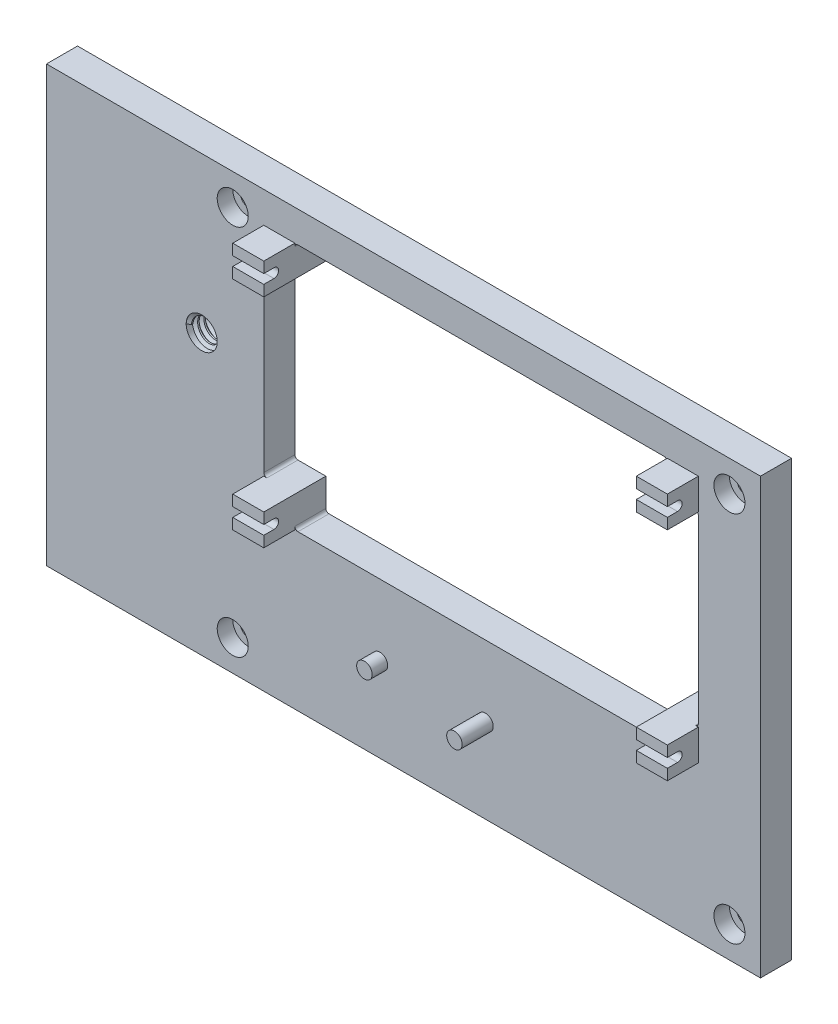
SolidWorks part; units mm, degrees
material "1.0558 (G300)"
ref_plane "Front Plane" through (0, 0, 0) normal (0, 0, 1) x (1, 0, 0)
ref_plane "Top Plane" through (0, 0, 0) normal (0, 1, 0) x (1, 0, 0)
ref_plane "Right Plane" through (0, 0, 0) normal (1, 0, 0) x (0, 0, -1)
sketch "Croquis1" plane through (0, 0, 0) normal (0, 0, 1) x (1, 0, 0)
  line L0 (-90, 0) -> (-70, 0) construction
  line L1 (90, -50) -> (-90, -50)
  line L2 (90, -50) -> (90, 50)
  line L3 (90, 50) -> (-90, 50)
  line L4 (-90, -50) -> (-90, 50)
  line L5 (-60, 30) -> (-70, 30)
  line L6 (60, 30) -> (60, 40)
  line L7 (90, 0) -> (70, 0) construction
  line L8 (0, 50) -> (0, 40) construction
  line L9 (0, -50) -> (0, -40) construction
  line L10 (-70, 0) -> (-70, 30)
  line L11 (-60, 40) -> (60, 40)
  line L12 (70, 30) -> (70, -30)
  line L13 (60, -40) -> (-60, -40)
  line L14 (-70, -30) -> (-70, 0)
  line L15 (-70, 0) -> (-60, 0) construction
  line L16 (0, 40) -> (0, 30) construction
  line L17 (-60, 40) -> (-60, 30)
  line L18 (60, 30) -> (70, 30)
  line L19 (-60, -30) -> (-70, -30)
  line L20 (-60, -30) -> (-60, -40)
  line L21 (60, -30) -> (60, -40)
  line L22 (60, -30) -> (70, -30)
  point P0 (0, 0)
  dimension "D1" = 180
  dimension "D2" = 100
  dimension "D3" = 20
  dimension "D4" = 20
  dimension "D5" = 10
  dimension "D6" = 10
  dimension "D7" = 10
  dimension "D8" = 10
  dimension "D9" = 10
  dimension "D10" = 10
  dimension "D11" = 120
  dimension "D12" = 10
  dimension "D13" = 10
  dimension "D14" = 10
extrude "Saliente-Extruir1" add sketch "Croquis1" along normal blind 10
sketch "Croquis2" plane through (0, 0, 10) normal (0, 0, 1) x (1, 0, 0)
  line L0 (80, 50) -> (80, 40) construction
  line L1 (90, 50) -> (-90, 50) construction
  line L2 (80, 40) -> (90, 40) construction
  line L3 (90, -50) -> (90, 50) construction
  line L4 (0, 24.0798) -> (0, -11.3446) construction
  line L5 (-15.0818, 0) -> (14.1818, 0) construction
  line L6 (-80, 40) -> (-90, 40) construction
  line L7 (-80, 50) -> (-80, 40) construction
  line L8 (80, -40) -> (90, -40) construction
  line L9 (80, -40) -> (80, -80)
  line L10 (-80, -40) -> (-90, -40) construction
  line L11 (-80, -40) -> (-80, -80)
  dimension "D1" = 10
  dimension "D2" = 10
sketch "Croquis4" plane through (0, 0, 10) normal (0, 0, 1) x (1, 0, 0)
  line L0 (0, 57.0372) -> (0, -6.8385) construction
  line L1 (-60, -30) -> (-70, -30)
  line L2 (-60, -30) -> (-60, -40)
  line L3 (-60, -40) -> (-70, -40)
  line L4 (-70, -30) -> (-70, -40)
  line L5 (-11.0869, 0) -> (22.8375, 0) construction
  line L6 (70, -30) -> (70, -40)
  line L7 (60, -40) -> (70, -40)
  line L8 (60, -30) -> (60, -40)
  line L9 (60, -30) -> (70, -30)
  line L10 (60, 30) -> (70, 30)
  line L11 (60, 30) -> (60, 40)
  line L12 (60, 40) -> (70, 40)
  line L13 (70, 30) -> (70, 40)
  line L14 (-60, 40) -> (-70, 40)
  line L15 (-70, 30) -> (-70, 40)
  line L16 (-60, 30) -> (-70, 30)
  line L17 (-60, 30) -> (-60, 40)
  dimension "D1" = 10
  dimension "D2" = 10
extrude "Saliente-Extruir2" add sketch "Croquis4" along normal blind 10
sketch "Croquis5" plane through (60, 0, 0) normal (-1, 0, 0) x (0, 0, 1)
  line L4 (10, 50) -> (10, -50) construction
  line L6 (10, 36.5) -> (11.5, 36.5) construction
  line L7 (10, 33.5) -> (11.5, 33.5) construction
  line L11 (20, 36.5) -> (20, 33.5)
  line L12 (20, 30) -> (20, 40) construction
  line L14 (20, 33.5) -> (16.7205, 33.5)
  line L15 (16.7205, 36.5) -> (20, 36.5)
  arc A1 (16.7205, 36.5) -> (16.7205, 33.5) centre (16.7205, 35) ccw
extrude "Cortar-Extruir1" cut sketch "Croquis5" against normal through all
mirror "Simetría1" about plane through (0, 0, 0) normal (0, 1, 0) of "Cortar-Extruir1"
mirror "Simetría2" about plane through (0, 0, 0) normal (1, 0, 0) of "Simetría1"
fillet "Redondeo1" radius 1 1 edges at (-70, -30, 5)
fillet "Redondeo2" radius 1 7 edges at (60, -40, 5) (70, -30, 5) (70, 30, 5) (60, 40, 5) (-60, 40, 5) (-70, 30, 5) (-60, -40, 5)
sketch "Croquis7" plane through (0, -50, 0) normal (0, -1, 0) x (1, 0, 0)
  line L1 (-90, 10) -> (90, 10)
  line L2 (-90, 10) -> (-90, 0)
  line L3 (-90, 0) -> (90, 0)
  line L4 (90, 10) -> (90, 0)
extrude "Saliente-Extruir4" add sketch "Croquis7" along normal blind 40
hole_wizard "Taladro1" positions "Croquis3D1" profile "Croquis3" legacy
sketch3d "Croquis3D1"
  point P0 (-80, 40, 10)
  point P3 (80, 40, 10)
  point P36 (-80, -80, 10)
  point P40 (80, -80, 10)
sketch "Croquis3" plane through (-80, 40, 10) normal (1, 0, 0) x (0, -1, 0)
  line L0 (0, 0) -> (0, 10)
  line L1 (0, 10) -> (2.5, 10)
  line L2 (2.5, 10) -> (2.5, 5)
  line L3 (2.5, 5) -> (5, 5)
  line L4 (5, 5) -> (5, 0)
  line L5 (5, 0) -> (0, 0)
  line L6 (0, 110) -> (0, -10) construction
  dimension "Diámetro" = 5
  dimension "Profundidad" = 10
  dimension "Diámetro de refrentado 1" = 10
  dimension "Profundidad de refrentado 1" = 5
sketch "Croquis8" plane through (0, 0, 10) normal (0, 0, 1) x (1, 0, 0)
  line L0 (-70, -40) -> (-70, -62.9) construction
  line L1 (-70, -62.9) -> (-32.5848, -62.9) construction
  circle A0 centre (-32.5848, -62.9) radius 2.5
  dimension "D1" = 5
  dimension "D2" = 22.9
  dimension "D3" = 37.4152
extrude "Saliente-Extruir5" add sketch "Croquis8" along normal blind 5
sketch "Croquis9" plane through (0, 0, 10) normal (0, 0, 1) x (1, 0, 0)
  line L0 (-30.0848, -62.9) -> (1.4152, -62.9) construction
  circle A0 centre (-32.5848, -62.9) radius 2.5 construction
  circle A1 centre (-32.5848, -62.9) radius 2.5 construction
  circle A2 centre (1.4152, -62.9) radius 2.5
  dimension "D2" = 5
  dimension "D1" = 31.5
extrude "Saliente-Extruir6" add sketch "Croquis9" along normal blind 10
sketch "Croquis10" plane through (-90, 0, 0) normal (-1, 0, 0) x (0, 0, 1)
  line L1 (0, 50) -> (10, 50)
  line L2 (0, 50) -> (0, -90)
  line L3 (0, -90) -> (10, -90)
  line L4 (10, 50) -> (10, -90)
extrude "Saliente-Extruir7" add sketch "Croquis10" along normal blind 50
sketch "Croquis11" plane through (0, 0, 10) normal (0, 0, 1) x (1, 0, 0)
  point P6 (-90, 0)
hole_wizard "Taladros de espiga de Ø10.0mm1" positions "Croquis3D2" profile "Croquis12" hole size "Ø10.0" standard "Ansi Metric"
sketch3d "Croquis3D2"
  point P0 (-90, 0, 10)
sketch "Croquis12" plane through (-90, 0, 10) normal (1, 0, 0) x (0, -1, 0)
  line L0 (0, 0) -> (0, 13.0043)
  line L1 (0, 13.0043) -> (5, 10)
  line L2 (5, 10) -> (5, 0)
  line L5 (5, 0) -> (0, 0)
  line L10 (0, 13.0043) -> (-5, 10) construction
  line L11 (0, -6.35) -> (0, 107.95) construction
  dimension "Diámetro de taladro" = 10
  dimension "Profundidad de taladro" = 10
  dimension "Ángulo de perforador" = 118
thread "Rosca1" pitch 2 method extrude profile "Perfil de rosca1" start angle 0, offset 0, length 8, pitch 2, diameter 10
ref_plane "Plano1" through (-95, 0, 10) normal (0, -1, 0) x (-1, 0, 0)
sketch "Perfil de rosca1" plane through (-95, 0, 10) normal (0, -1, 0) x (-1, 0, 0)
  line L0 (0, 0) -> (0, 2) construction
  line L11 (0, 0) -> (0, 1.75)
  line L12 (0, 1.75) -> (-1.0825, 1.125)
  line L13 (-1.0825, 1.125) -> (-1.0825, 0.625)
  line L15 (-1.0825, 0.625) -> (0, 0)
  line L17 (-1.0825, 0.875) -> (0, 0.875) construction
  point P2 (0, 0)
  dimension "Pitch" = 2
  dimension "Profile_Angle" = 60
  dimension "Profile_Land" = 0.5
  dimension "Profile_Height" = 1.0825
